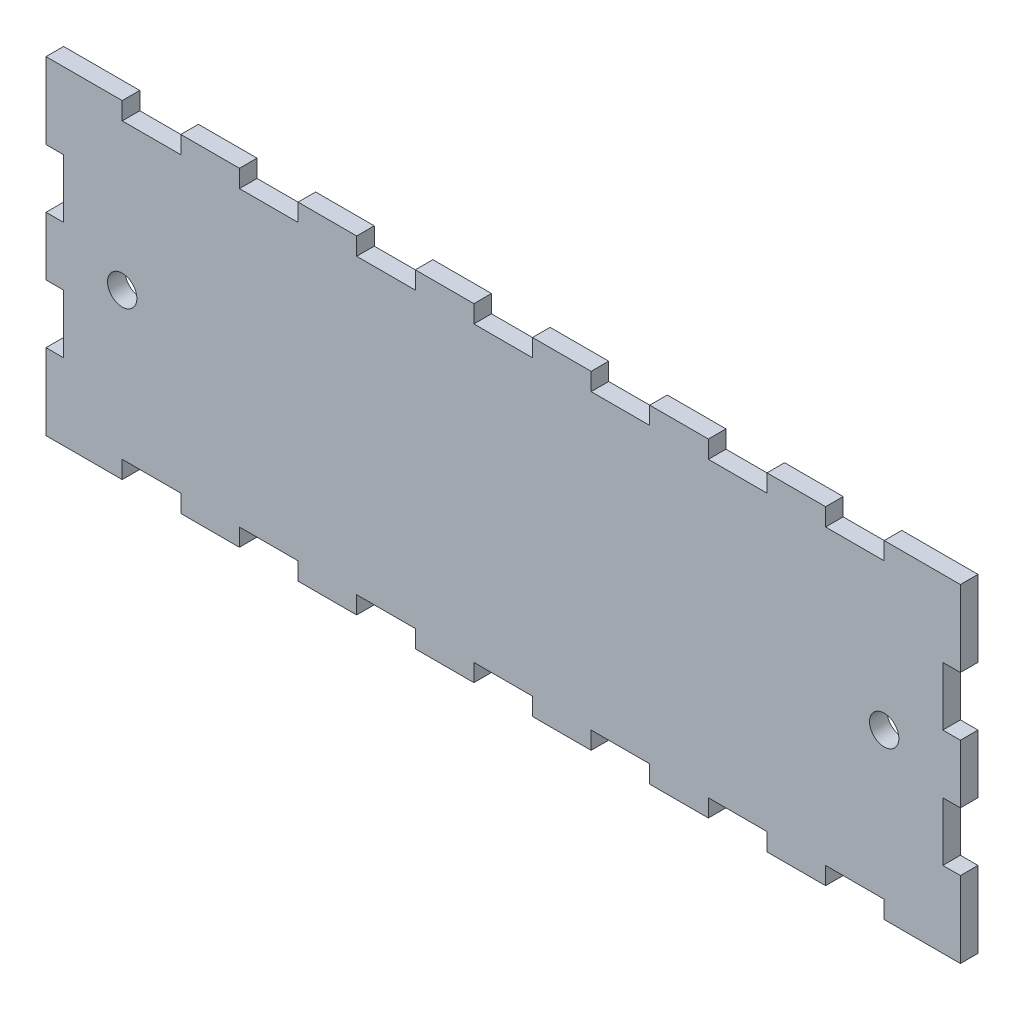
SolidWorks part; units mm, degrees
ref_plane "Front Plane" through (0, 0, 0) normal (0, 0, 1) x (1, 0, 0)
ref_plane "Top Plane" through (0, 0, 0) normal (0, 1, 0) x (1, 0, 0)
ref_plane "Right Plane" through (0, 0, 0) normal (1, 0, 0) x (0, 0, -1)
sketch "Sketch1" plane through (0, 0, 0) normal (0, 0, 1) x (1, 0, 0)
  line L0 (15, 28) -> (15, 25)
  line L1 (-76.5, 26.5) -> (76.5, 26.5) construction
  line L2 (-76.5, 26.5) -> (-76.5, -26.5) construction
  line L3 (-76.5, -26.5) -> (76.5, -26.5) construction
  line L4 (76.5, 26.5) -> (76.5, -26.5) construction
  line L5 (-76.5, 26.5) -> (76.5, -26.5) construction
  line L6 (-76.5, -26.5) -> (76.5, 26.5) construction
  line L7 (-5, 28) -> (5, 28) construction
  line L8 (-5, 28) -> (-5, 25)
  line L9 (-5, 25) -> (5, 25)
  line L10 (5, 28) -> (5, 25)
  line L11 (-5, 28) -> (5, 25) construction
  line L12 (-5, 25) -> (5, 28) construction
  line L13 (15, 25) -> (25, 25)
  line L14 (25, 28) -> (25, 25)
  line L15 (35, 28) -> (35, 25)
  line L16 (35, 25) -> (45, 25)
  line L17 (45, 28) -> (45, 25)
  line L18 (55, 28) -> (55, 25)
  line L19 (55, 25) -> (65, 25)
  line L20 (65, 28) -> (65, 25)
  line L21 (5, 28) -> (15, 28)
  line L22 (25, 28) -> (35, 28)
  line L23 (45, 28) -> (55, 28)
  line L24 (65, 28) -> (78, 28)
  line L25 (-25, 25) -> (-15, 25)
  line L26 (-25, 28) -> (-25, 25)
  line L27 (-15, 28) -> (-15, 25)
  line L28 (-45, 25) -> (-35, 25)
  line L29 (-45, 28) -> (-45, 25)
  line L30 (-35, 28) -> (-35, 25)
  line L31 (-65, 25) -> (-55, 25)
  line L32 (-65, 28) -> (-65, 25)
  line L33 (-55, 28) -> (-55, 25)
  line L34 (-55, 28) -> (-45, 28)
  line L35 (-35, 28) -> (-25, 28)
  line L36 (-15, 28) -> (-5, 28)
  line L37 (-65, 28) -> (-78, 28)
  line L38 (0, 0) -> (10.7491, 0) construction
  line L39 (0, 0) -> (0, 9.6256) construction
  line L40 (65, -28) -> (78, -28)
  line L41 (65, -28) -> (65, -25)
  line L42 (55, -25) -> (65, -25)
  line L43 (55, -28) -> (55, -25)
  line L44 (45, -28) -> (55, -28)
  line L45 (45, -28) -> (45, -25)
  line L46 (35, -25) -> (45, -25)
  line L47 (35, -28) -> (35, -25)
  line L48 (25, -28) -> (35, -28)
  line L49 (25, -28) -> (25, -25)
  line L50 (15, -25) -> (25, -25)
  line L51 (15, -28) -> (15, -25)
  line L52 (5, -28) -> (15, -28)
  line L53 (5, -28) -> (5, -25)
  line L54 (-5, -25) -> (5, -25)
  line L55 (-5, -28) -> (-5, -25)
  line L56 (-15, -28) -> (-5, -28)
  line L57 (-15, -28) -> (-15, -25)
  line L58 (-25, -25) -> (-15, -25)
  line L59 (-25, -28) -> (-25, -25)
  line L60 (-35, -28) -> (-25, -28)
  line L61 (-35, -28) -> (-35, -25)
  line L62 (-45, -25) -> (-35, -25)
  line L63 (-45, -28) -> (-45, -25)
  line L64 (-55, -28) -> (-45, -28)
  line L65 (-55, -28) -> (-55, -25)
  line L66 (-65, -25) -> (-55, -25)
  line L67 (-65, -28) -> (-65, -25)
  line L68 (-65, -28) -> (-78, -28)
  line L69 (78, 28) -> (78, 15)
  line L70 (78, -28) -> (78, -15)
  line L71 (75, -5) -> (78, -5)
  line L72 (75, -5) -> (75, -15)
  line L73 (75, -15) -> (78, -15)
  line L74 (78, -5) -> (78, -15) construction
  line L75 (75, -5) -> (78, -15) construction
  line L76 (75, -15) -> (78, -5) construction
  line L77 (75, 15) -> (75, 5)
  line L78 (75, 15) -> (78, 15)
  line L79 (75, 5) -> (78, 5)
  line L80 (78, -5) -> (78, 5)
  line L81 (-78, -28) -> (-78, -15)
  line L82 (-75, -15) -> (-78, -15)
  line L83 (-75, -5) -> (-75, -15)
  line L84 (-75, -5) -> (-78, -5)
  line L85 (-78, -5) -> (-78, 5)
  line L86 (-75, 5) -> (-78, 5)
  line L87 (-75, 15) -> (-75, 5)
  line L88 (-75, 15) -> (-78, 15)
  line L89 (-78, 28) -> (-78, 15)
  point P0 (0, 0)
  point P6 (0, 26.5)
  point P70 (76.5, -10)
  dimension "D1" = 153
  dimension "D2" = 53
  dimension "D3" = 10
  dimension "D4" = 3
  dimension "D7" = 10
  dimension "D9" = 10
  dimension "D10" = 13
  dimension "D11" = 10
  dimension "D12" = 13
  dimension "D13" = 13
  dimension "D5" = 4
  dimension "D8" = 4
  dimension "D14" = 2
extrude "Boss-Extrude1" add sketch "Sketch1" along normal blind 3
sketch "Sketch2" plane through (0, 0, 3) normal (0, 0, 1) x (1, 0, 0)
  line L0 (0, 0) -> (-65, 0) construction
  line L1 (0, 0) -> (0, 10.506) construction
  circle A0 centre (-65, 0) radius 2.5
  circle A1 centre (65, 0) radius 2.5
  dimension "D1" = 5
  dimension "D2" = 65
extrude "Cut-Extrude1" cut sketch "Sketch2" against normal blind 3
